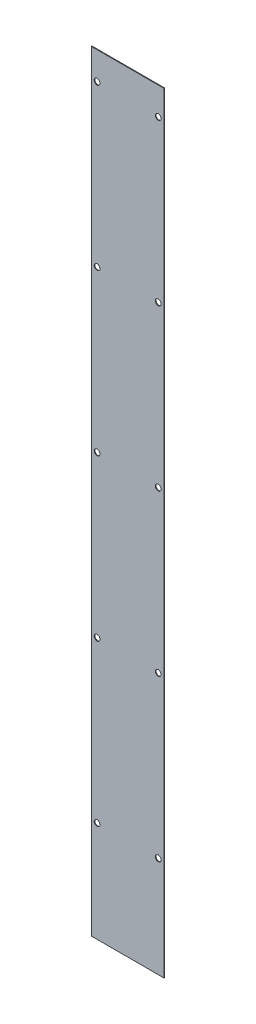
SolidWorks part; units mm, degrees
ref_plane "Front Plane" through (0, 0, 0) normal (0, 0, 1) x (1, 0, 0)
ref_plane "Top Plane" through (0, 0, 0) normal (0, 1, 0) x (1, 0, 0)
ref_plane "Right Plane" through (0, 0, 0) normal (1, 0, 0) x (0, 0, -1)
sketch "Sketch1" plane through (0, 0, 0) normal (0, 0, 1) x (1, 0, 0)
  line L1 (0, 0) -> (76, 0)
  line L2 (0, 0) -> (0, 806.5)
  line L3 (0, 806.5) -> (76, 806.5)
  line L4 (76, 0) -> (76, 806.5)
  dimension "D1" = 806.5
  dimension "D2" = 76
base flange "Base-Flange1" sketch "Sketch1" thickness 0.7 reverse thickness direction no parameters "D1"=1
sketch "Sketch2" plane through (0, 0, 0) normal (0, 0, 1) x (1, 0, 0)
  line L1 (76, 806.5) -> (0, 806.5) construction
  line L2 (38, 806.5) -> (38, 748.5) construction
  line L4 (76, 0) -> (76, 806.5) construction
  circle A12 centre (70, 777.5) radius 3
  circle A13 centre (70, 609.5) radius 3
  circle A14 centre (70, 441.5) radius 3
  circle A15 centre (70, 273.5) radius 3
  circle A16 centre (70, 105.5) radius 3
  circle A17 centre (6, 105.5) radius 3
  circle A18 centre (6, 273.5) radius 3
  circle A19 centre (6, 441.5) radius 3
  circle A20 centre (6, 609.5) radius 3
  circle A21 centre (6, 777.5) radius 3
  dimension "D1" = 6
  dimension "D2" = 6
  dimension "D3" = 29
  dimension "D4" = 5
extrude "Cut-Extrude1" cut sketch "Sketch2" against normal blind 10 normal cut yes
sketch "Bend-Lines1" [suppressed] plane through (0, 0, 0) normal (0, 1, 0) x (1, 0, 0)
sketch "Bounding-Box1" [suppressed] plane through (0, 0, 0) normal (0, 1, 0) x (1, 0, 0)
sheet metal parameters "Sheet-Metal1" thickness 0.7 parameters "D1"=1
flat pattern "Flat-Pattern1" [suppressed]
sketch "Bend-Lines2" plane through (0, 0, 0) normal (0, 1, 0) x (1, 0, 0)
sketch3d "Bounding-Box2" [suppressed]
  line L0 (240, 707, 0) -> (240, 0, 0) construction
  line L1 (0, 707, 0) -> (0, 0, 0) construction
  line L2 (240, 707, 0) -> (0, 707, 0) construction
  line L3 (240, 0, 0) -> (0, 0, 0) construction
sheet metal parameters "Sheet-Metal2" thickness 0.7 parameters "D1"=1
flat pattern "Flat-Pattern1"
sketch "Bend-Lines2" plane through (0, 0, 0) normal (0, 1, 0) x (1, 0, 0)
sketch3d "Bounding-Box2" [suppressed]
  line L0 (85, 806.5, 0) -> (85, 0, 0) construction
  line L1 (0, 806.5, 0) -> (0, 0, 0) construction
  line L2 (85, 806.5, 0) -> (0, 806.5, 0) construction
  line L3 (85, 0, 0) -> (0, 0, 0) construction
